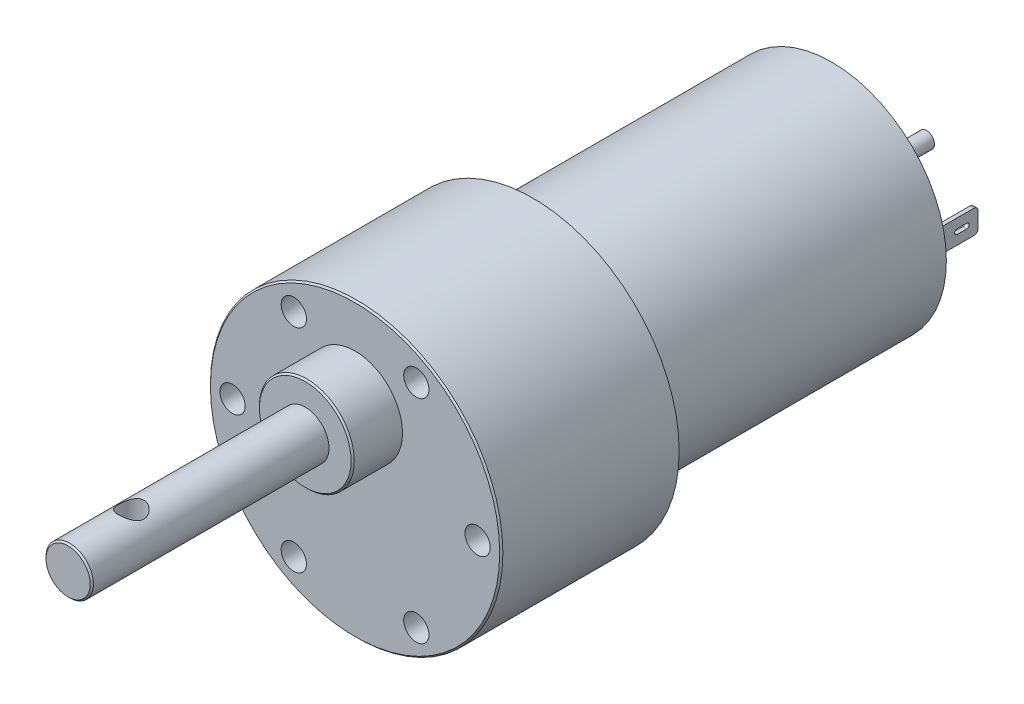
SolidWorks part; units mm, degrees
material "1060 Alloy"
ref_plane "Front Plane" through (0, 0, 0) normal (0, 0, 1) x (1, 0, 0)
ref_plane "Top Plane" through (0, 0, 0) normal (0, 1, 0) x (1, 0, 0)
ref_plane "Right Plane" through (0, 0, 0) normal (1, 0, 0) x (0, 0, -1)
sketch "Sketch1" plane through (0, 0, 0) normal (0, 0, 1) x (1, 0, 0)
  circle A0 centre (0, 0) radius 18.5
  dimension "D1" = 37
extrude "Boss-Extrude1" add sketch "Sketch1" along normal blind 22.5
sketch "Sketch2" plane through (0, 0, 22.5) normal (0, 0, 1) x (1, 0, 0)
  line L0 (-18.5, 0) -> (18.5, 0) construction
  line L1 (0, 18.5) -> (0, -18.5) construction
  line L2 (11.1332, 19.2832) -> (-10.7359, -18.5952) construction
  line L3 (-11.3747, 19.7016) -> (11.6905, -20.2486) construction
  circle A0 centre (0, 0) radius 18.5 construction
  circle A1 centre (0, 0) radius 15.5 construction
  circle A2 centre (-7.75, 13.4234) radius 1.6
  circle A3 centre (7.75, 13.4234) radius 1.6
  circle A4 centre (-15.5, 0) radius 1.6
  circle A5 centre (-7.75, -13.4234) radius 1.6
  circle A6 centre (7.75, -13.4234) radius 1.6
  circle A7 centre (15.5, 0) radius 1.6
  dimension "D3" = 31
  dimension "D4" = 3.2
  dimension "D1" = 120
  dimension "D2" = 120
extrude "Cut-Extrude1" cut sketch "Sketch2" against normal blind 3.5
sketch "Sketch3" plane through (0, 0, 22.5) normal (0, 0, 1) x (1, 0, 0)
  line L0 (0, 0) -> (0, 18.5) construction
  circle A0 centre (0, 0) radius 18.5 construction
  circle A1 centre (0, 7) radius 6
  circle A2 centre (0, 7) radius 3
  dimension "D1" = 12
  dimension "D3" = 6
  dimension "D2" = 7
extrude "Boss-Extrude2" add sketch "Sketch3" along normal blind 36.3 contours A2 L0 | L0 A2 region at (-1.2732, 7, 22.5) region at (1.2732, 7, 22.5)
extrude "Boss-Extrude3" add sketch "Sketch3<3>" along normal blind 6.3 contours A1 L0 A2 | L0 A1 A2 region at (-5.8658, 7, 22.5) region at (0.1342, 2.5, 22.5)
sketch "Sketch3<3>" plane through (0, 0, 22.5) normal (0, 0, 1) x (1, 0, 0) same geometry as "Sketch3"
sketch "Sketch4" plane through (0, 0, 0) normal (0, 0, -1) x (-1, 0, 0)
  circle A0 centre (0, 0) radius 14.5
  dimension "D1" = 29
extrude "Boss-Extrude4" add sketch "Sketch4" along normal blind 37.8
sketch "Sketch5" plane through (0, 0, -37.8) normal (0, 0, -1) x (-1, 0, 0)
  line L0 (-14.5, 0) -> (14.5, 0) construction
  circle A0 centre (0, 0) radius 5
  circle A1 centre (0, 0) radius 14.5 construction
  dimension "D1" = 10
extrude "Boss-Extrude5" add sketch "Sketch5" along normal blind 3
sketch "Sketch6" plane through (0, 0, -40.8) normal (0, 0, -1) x (-1, 0, 0)
  circle A0 centre (0, 0) radius 1
  dimension "D1" = 2
extrude "Boss-Extrude6" add sketch "Sketch6" along normal blind 9
sketch "Sketch7" plane through (0, 0, -37.8) normal (0, 0, -1) x (-1, 0, 0)
  line L0 (-14.5, 0) -> (14.5, 0) construction
  line L1 (0, 0) -> (0, -10.7163) construction
  line L2 (-12, 1.5) -> (-11.5, 1.5)
  line L3 (-12, 1.5) -> (-12, -1.5)
  line L4 (-12, -1.5) -> (-11.5, -1.5)
  line L5 (-11.5, 1.5) -> (-11.5, -1.5)
  line L6 (12, 1.5) -> (11.5, 1.5)
  line L7 (12, -1.5) -> (11.5, -1.5)
  line L8 (12, 1.5) -> (12, -1.5)
  line L9 (11.5, 1.5) -> (11.5, -1.5)
  circle A0 centre (0, 0) radius 14.5 construction
  circle A1 centre (0, 0) radius 14.5 construction
  dimension "D1" = 3
  dimension "D2" = 1.5
  dimension "D3" = 0.5
  dimension "D4" = 11.5
extrude "Boss-Extrude7" add sketch "Sketch7" along normal blind 6.5
sketch "Sketch8" plane through (12, 0, 0) normal (1, 0, 0) x (0, 0, -1)
  line L0 (42.8651, 0) -> (41.6651, 0) construction
  line L1 (42.8651, -0.3201) -> (41.6651, -0.3201)
  line L2 (42.8651, 0.3201) -> (41.6651, 0.3201)
  line L3 (42.8651, 0) -> (44.3, 0) construction
  line L4 (44.3, 1.5) -> (44.3, -1.5) construction
  arc A0 (42.8651, -0.3201) -> (42.8651, 0.3201) centre (42.8651, 0) ccw
  arc A1 (41.6651, 0.3201) -> (41.6651, -0.3201) centre (41.6651, 0) ccw
  point P2 (42.2651, 0)
  dimension "D1" = 1.2
extrude "Cut-Extrude2" cut sketch "Sketch8" against normal blind 0.5
mirror "Mirror2" about plane through (0, 0, 0) normal (1, 0, 0) of "Cut-Extrude2"
fillet "Fillet1" radius 0.5 4 edges at (-11.75, 1.5, -44.3) (-11.75, -1.5, -44.3) (11.75, 1.5, -44.3) (11.75, -1.5, -44.3)
chamfer "Chamfer1" distance 0.2 angle 45 3 edges at (18.5, 0, 22.5) (6, 7, 28.8) (3, 7, 58.8)
ref_plane "Plane1" through (0, 7, 0) normal (0, 1, 0) x (1, 0, 0)
sketch "Sketch9" plane through (0, 7, 0) normal (0, 1, 0) x (1, 0, 0)
  line L0 (0, -58.6) -> (0, -28.8) construction
  line L1 (3, -58.6) -> (-3, -58.6) construction
  line L2 (-2.8, -58.8) -> (2.8, -58.8) construction
  line L3 (-3, -28.8) -> (3, -28.8) construction
  circle A0 centre (0, -50.8) radius 1.6
  dimension "D1" = 3.2
  dimension "D2" = 8
extrude "Cut-Extrude3" cut sketch "Sketch9" against normal through all and the other way through all
scale "Scale1" scale about centroid uniform scaling yes scale factor 0.6757
